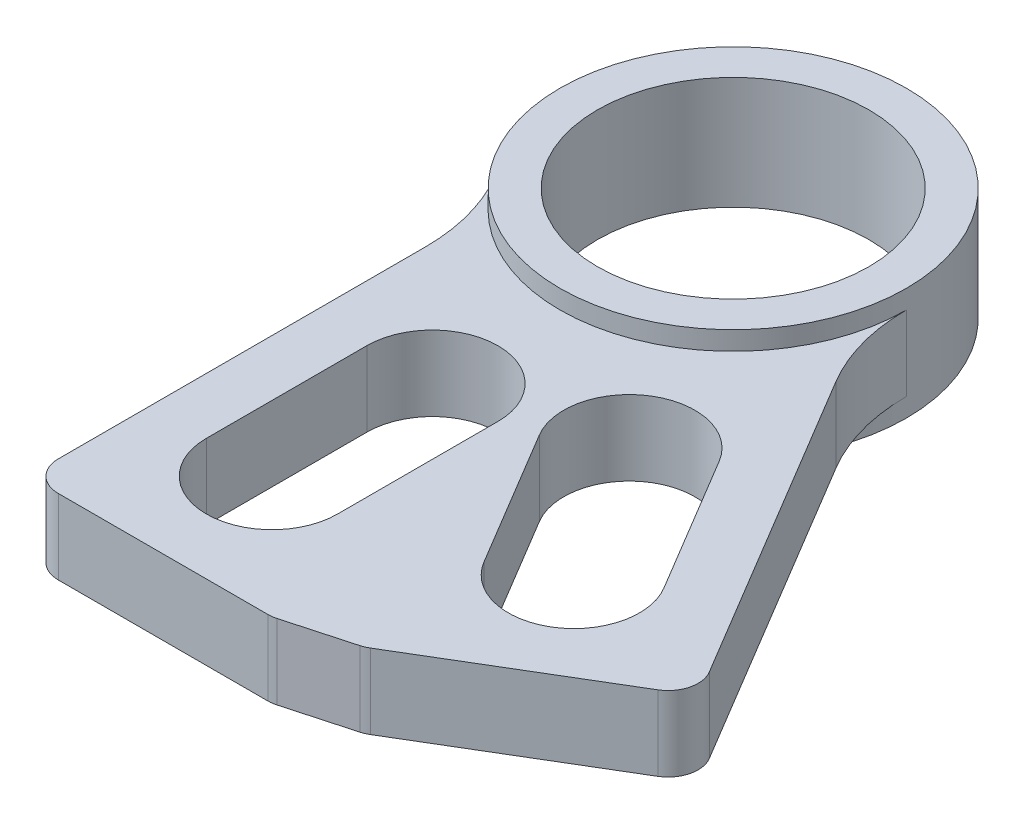
SolidWorks part; units mm, degrees
ref_plane "Front Plane" through (0, 0, 0) normal (0, 0, 1) x (1, 0, 0)
ref_plane "Top Plane" through (0, 0, 0) normal (0, 1, 0) x (1, 0, 0)
ref_plane "Right Plane" through (0, 0, 0) normal (1, 0, 0) x (0, 0, -1)
sketch "Sketch1" plane through (0, 0, 0) normal (0, 1, 0) x (1, 0, 0)
  line L0 (0, 0) -> (0, -49.3903) construction
  line L1 (0, 0) -> (25.3394, -42.3948) construction
  line L2 (0, -39.0716) -> (0, -25.4826) construction
  line L3 (-5.5562, -39.0716) -> (-5.5562, -25.4826)
  line L4 (5.5563, -39.0716) -> (5.5563, -25.4826)
  line L5 (20.0454, -33.5375) -> (13.0737, -21.8733) construction
  line L6 (15.2762, -36.3881) -> (8.3044, -24.7239)
  line L7 (24.8147, -30.6869) -> (17.843, -19.0227)
  line L8 (0, -49.3903) -> (0, -44.6278) construction
  line L9 (25.3394, -42.3948) -> (22.896, -38.3068) construction
  line L10 (-10.3187, -49.3903) -> (10.3188, -49.3903)
  line L11 (16.4822, -47.6887) -> (34.1966, -37.1008)
  line L12 (-10.3187, -49.3903) -> (-10.3187, -10.4432)
  line L13 (10.3188, -49.3903) -> (10.3188, -37.3768)
  line L14 (34.1966, -37.1008) -> (14.2151, -3.6701)
  line L15 (16.4822, -47.6887) -> (10.3188, -37.3768)
  line L16 (185.4182, -310.2186) -> (14.7507, -24.6791) construction
  line L17 (10.3188, -49.3903) -> (16.4822, -47.6887)
  line L22 (0, 0) -> (10.3188, -37.3768) construction
  circle A0 centre (0, 0) radius 11.5062
  circle A1 centre (0, 0) radius 14.6812
  arc A2 (-5.5562, -39.0716) -> (5.5563, -39.0716) centre (0, -39.0716) ccw
  arc A3 (5.5563, -25.4826) -> (-5.5562, -25.4826) centre (0, -25.4826) ccw
  arc A4 (15.2762, -36.3881) -> (24.8147, -30.6869) centre (20.0454, -33.5375) ccw
  arc A5 (17.843, -19.0227) -> (8.3044, -24.7239) centre (13.0737, -21.8733) ccw
  point P8 (0, -32.2771)
  point P13 (16.5596, -27.7054)
  point P25 (0, -49.3903)
  point P27 (25.3394, -42.3948)
  dimension "D2" = 29.3624
  dimension "D3" = 4.7625
  dimension "D4" = 4.7625
  dimension "D5" = 13.589
  dimension "D6" = 49.3903
  dimension "D7" = 20.6375
extrude "Bearing_Insert_Extrude" add sketch "Sketch1" along normal mid plane 9.525 contours A1 A0 region at (-5.4988, 0, -13.1636)
extrude "Apex_Slot_Insert_Extrude" add sketch "Sketch1<4>" along normal mid plane 6.35 contours A1 L12 L10 L13 L15 L11 L14 A5 L7 A4 L6 A3 L4 A2 L3 | L13 L17 L15 region at (8.3301, 0, 30.1737) region at (12.3732, 0, 44.8186)
sketch "Sketch1<4>" plane through (0, 0, 0) normal (0, 1, 0) x (1, 0, 0) same geometry as "Sketch1"
fillet "Fillet1" radius 16.002 2 edges at (14.2151, 0, 3.6701) (-10.3187, 0, 10.4432)
fillet "Fillet2" radius 2.54 4 edges at (34.1966, 0, 37.1008) (-10.3187, 0, 49.3903) (16.4822, 0, 47.6887) (10.3188, 0, 49.3903)
equation "\"Apex_thickness\"= .25"
equation "\"Bearing_diameter\"= 0.906in"
equation "\"A-arm_angle\"= 39.1893"
equation "\"D1@Sketch1\"=\"Bearing_diameter\""
equation "\"D1@Apex_Slot_Insert_Extrude\"=\"Apex_thickness\""
